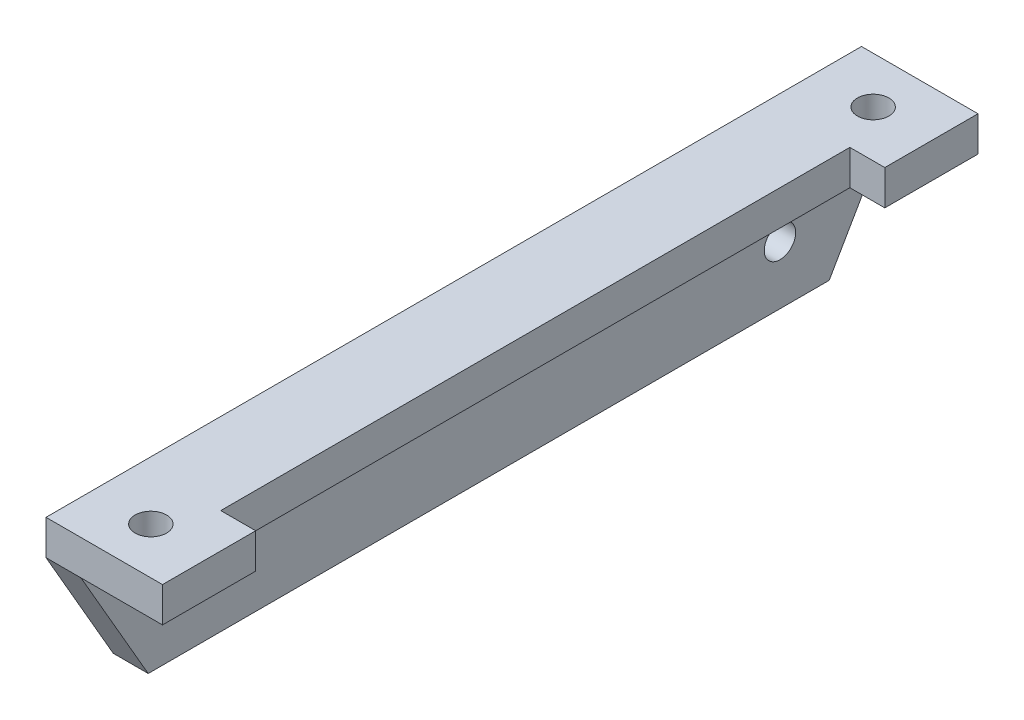
SolidWorks part; units mm, degrees
ref_plane "Front Plane" through (0, 0, 0) normal (0, 0, 1) x (1, 0, 0)
ref_plane "Top Plane" through (0, 0, 0) normal (0, 1, 0) x (1, 0, 0)
ref_plane "Right Plane" through (0, 0, 0) normal (1, 0, 0) x (0, 0, -1)
sketch "Sketch1" plane through (0, 0, 0) normal (0, 1, 0) x (1, 0, 0)
  line L1 (0, -35) -> (10, -35)
  line L2 (0, -35) -> (0, 35)
  line L3 (0, 35) -> (10, 35)
  line L4 (10, -35) -> (10, 35)
  point P4 (0, 0)
  dimension "D1" = 10
  dimension "D2" = 70
extrude "Boss-Extrude1" add sketch "Sketch1" along normal blind 3
sketch "Sketch2" plane through (0, 0, 0) normal (0, -1, 0) x (1, 0, 0)
  line L0 (10, -35) -> (0, -35) construction
  line L1 (0, 35) -> (3, 35)
  line L2 (0, 35) -> (0, -35)
  line L3 (0, -35) -> (3, -35)
  line L4 (3, 35) -> (3, -35)
  dimension "D1" = 3
extrude "Boss-Extrude2" add sketch "Sketch2" along normal blind 10
sketch "Sketch3" plane through (0, 3, 0) normal (0, 1, 0) x (1, 0, 0)
  line L0 (0, 35) -> (0, -35) construction
  circle A0 centre (5, 31) radius 1.35
  circle A1 centre (5, -31) radius 1.35
  dimension "D1" = 62
  dimension "D3" = 2.7
  dimension "D4" = 5
  dimension "D2" = 31
extrude "Cut-Extrude1" cut sketch "Sketch3" against normal through all both and the other way through all
sketch "Sketch4" plane through (3, 0, 0) normal (1, 0, 0) x (0, 0, -1)
  circle A0 centre (25, -5) radius 1.35
  circle A1 centre (-25, -5) radius 1.35
  dimension "D2" = 25
  dimension "D4" = 2.7
  dimension "D1" = 25
  dimension "D3" = 5
extrude "Cut-Extrude2" cut sketch "Sketch4" against normal blind 10
chamfer "Chamfer1" distance 10 angle 30 2 edges at (1.5, -10, -35) (1.5, -10, 35) first distance on face at (4.3333, -2.3333, -35) first distance on face at (4.3333, -2.3333, 35)
sketch "Sketch5" plane through (0, 3, 0) normal (0, 1, 0) x (1, 0, 0)
  line L0 (10, -35) -> (10, 35) construction
  line L1 (10, 27) -> (7, 27)
  line L2 (10, 27) -> (10, -27)
  line L3 (10, -27) -> (7, -27)
  line L4 (7, 27) -> (7, -27)
  circle A0 centre (5, 31) radius 1.35 construction
  circle A1 centre (5, -31) radius 1.35 construction
  dimension "D2" = 4
  dimension "D1" = 3
  dimension "D3" = 4
extrude "Cut-Extrude3" cut sketch "Sketch5" against normal blind 10
